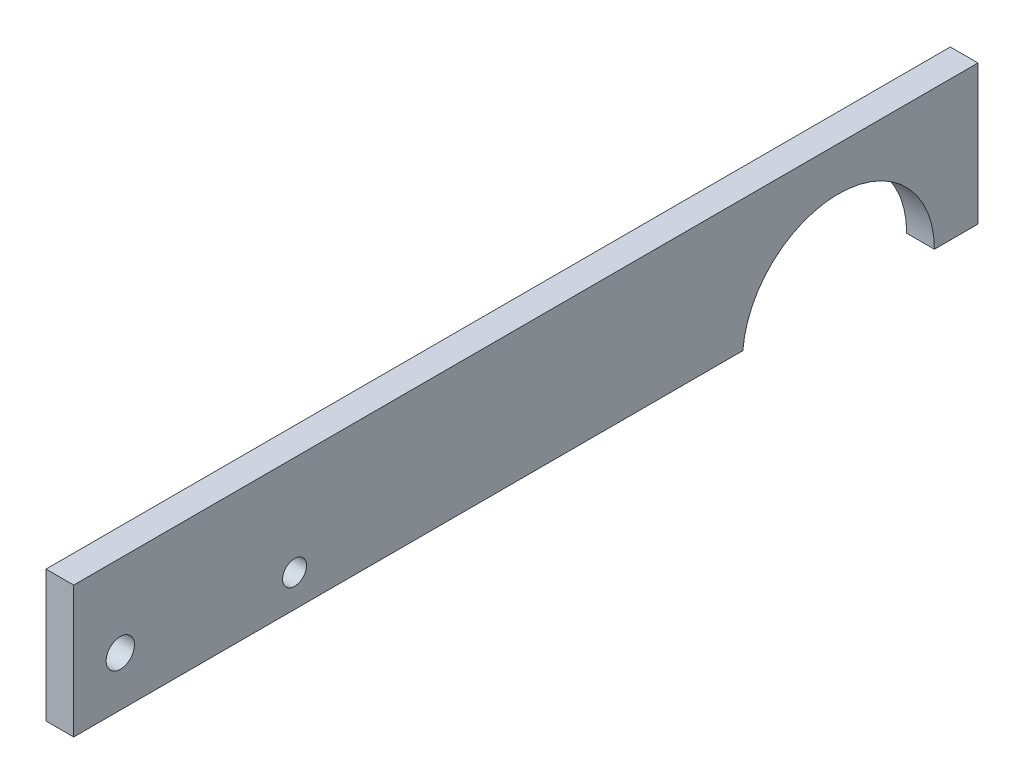
SolidWorks part; units mm, degrees
ref_plane "Front Plane" through (0, 0, 0) normal (0, 0, 1) x (1, 0, 0)
ref_plane "Top Plane" through (0, 0, 0) normal (0, 1, 0) x (1, 0, 0)
ref_plane "Right Plane" through (0, 0, 0) normal (1, 0, 0) x (0, 0, -1)
sketch "Sketch1" plane through (0, 0, 0) normal (1, 0, 0) x (0, 0, -1)
  line L0 (-175.3536, 32) -> (32, 32)
  line L1 (32, 32) -> (32, 0)
  line L2 (32, 0) -> (22, 0)
  line L9 (-175.3536, 1.8193) -> (-21.9246, 1.8193)
  line L10 (-175.3536, 32) -> (-175.3536, 1.8193)
  arc A0 (-21.9246, 1.8193) -> (22, 0) centre (0, 0) cw
  circle A1 centre (-164.67, 13.1797) radius 3.25
  circle A2 centre (-124.7114, 9.1881) radius 2.75
  dimension "D1" = 6.5
  dimension "D6" = 22
  dimension "D2" = 32
  dimension "D4" = 5.5
  dimension "D3" = 196.67
  dimension "D5" = 10
  dimension "D7" = 39.9586
extrude "Boss-Extrude1" add sketch "Sketch1" along normal blind 6.35
